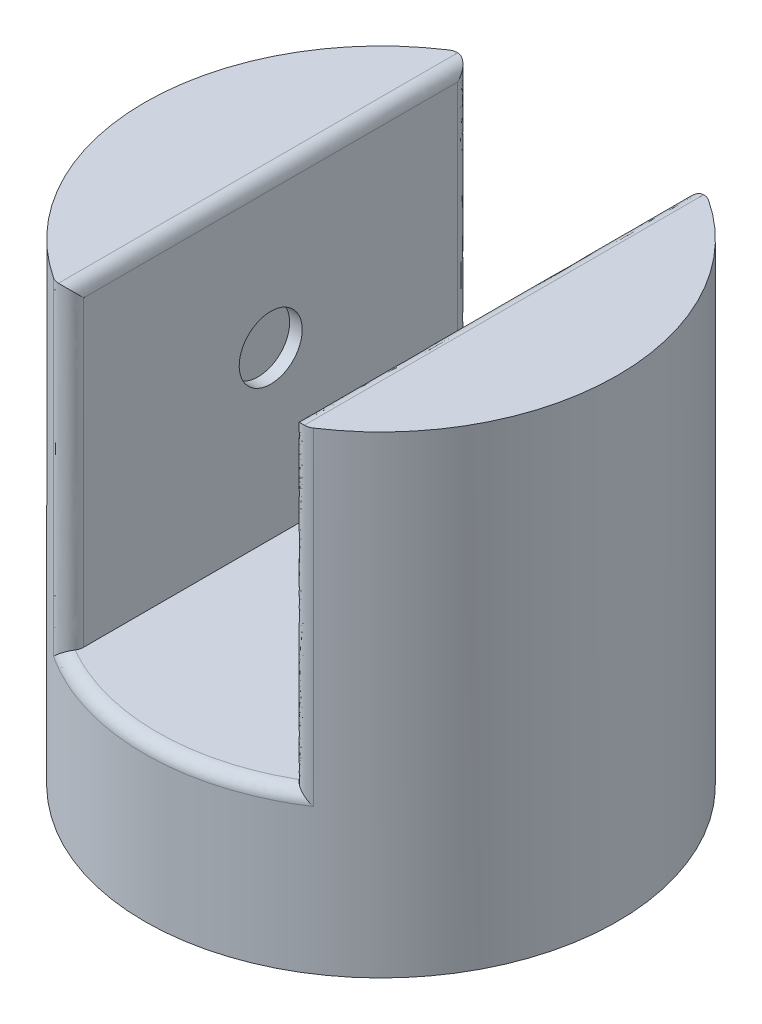
SolidWorks part; units mm, degrees
ref_plane "Ebene vorne" through (0, 0, 0) normal (0, 0, 1) x (1, 0, 0)
ref_plane "Ebene oben" through (0, 0, 0) normal (0, 1, 0) x (1, 0, 0)
ref_plane "Ebene rechts" through (0, 0, 0) normal (1, 0, 0) x (0, 0, -1)
sketch "Skizze1" plane through (0, 0, 0) normal (0, 1, 0) x (1, 0, 0)
  circle A0 centre (0, 0) radius 37.5
  dimension "D1" = 75
extrude "Aufsatz-Linear austragen1" add sketch "Skizze1" along normal blind 75
sketch "Skizze2" plane through (0, 0, 0) normal (0, 0, 1) x (1, 0, 0)
  line L0 (37.5, 75) -> (-37.5, 75) construction
  line L1 (-17.5, 75) -> (17.5, 75)
  line L2 (-17.5, 75) -> (-17.5, 25)
  line L3 (-17.5, 25) -> (17.5, 25)
  line L4 (17.5, 75) -> (17.5, 25)
  line L5 (-37.5, 75) -> (-37.5, 0) construction
  line L6 (37.5, 0) -> (37.5, 75) construction
  dimension "D1" = 20
  dimension "D2" = 35
  dimension "D3" = 50
  dimension "D4" = 20
extrude "Schnitt-Linear austragen1" cut sketch "Skizze2" against normal blind 75 and the other way blind 75
fillet "Verrundung1" radius 2 8 edges at (17.5, 75, 0) (17.5, 50, 33.1662) (0, 25, 37.5) (-17.5, 50, 33.1662) (-17.5, 75, 0) (-17.5, 50, -33.1662) (17.5, 50, -33.1662) (0, 25, -37.5) first distance on face at (27.5, 75, 0) first distance on face at (0, 0, 37.5) first distance on face at (-27.5, 75, 0)
sketch "Skizze3" plane through (0, 0, 0) normal (0, -1, 0) x (-1, 0, 0)
  circle A0 centre (0, 0) radius 5
extrude "Aufsatz-Linear austragen2" add sketch "Skizze3" along normal blind 20
sketch "Skizze4" plane through (-17.5, 0, 0) normal (1, 0, 0) x (0, 0, -1)
  circle A0 centre (0, 51.3087) radius 5
extrude "Schnitt-Linear austragen2" cut sketch "Skizze4" against normal blind 2
